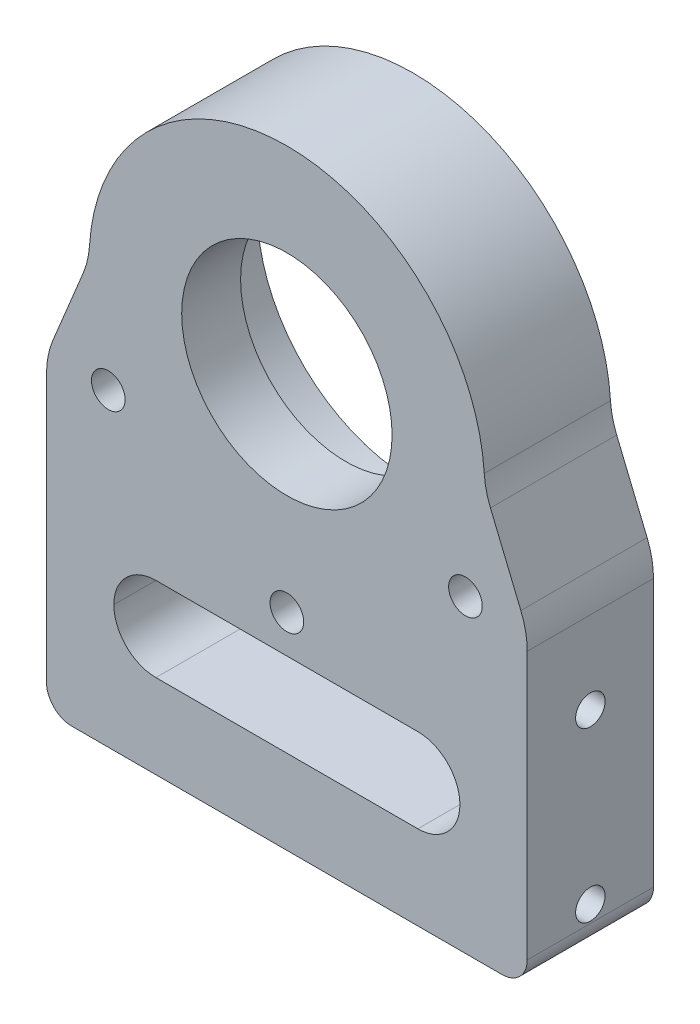
SolidWorks part; units mm, degrees
material "5052-H34"
ref_plane "正面" through (0, 0, 0) normal (0, 0, 1) x (1, 0, 0)
ref_plane "平面" through (0, 0, 0) normal (0, 1, 0) x (1, 0, 0)
ref_plane "右側面" through (0, 0, 0) normal (1, 0, 0) x (0, 0, -1)
sketch "ｽｹｯﾁ1" plane through (0, 0, 0) normal (0, 0, 1) x (1, 0, 0)
  line L1 (28.56, 15) -> (-28.56, 15)
  line L2 (28.56, 15) -> (28.56, -15)
  line L3 (28.56, -15) -> (-28.56, -15)
  line L4 (-28.56, 15) -> (-28.56, -15)
  line L5 (28.56, 15) -> (-28.56, -15) construction
  line L6 (28.56, -15) -> (-28.56, 15) construction
  point P0 (0, 0)
  dimension "D1" = 30
  dimension "D2" = 57.12
extrude "ﾎﾞｽ - 押し出し1" add sketch "ｽｹｯﾁ1" along normal blind 15
sketch "ｽｹｯﾁ2" plane through (-28.56, 0, 0) normal (-1, 0, 0) x (0, 0, 1)
  line L0 (7.5, 15) -> (7.5, -15) construction
  line L1 (15, 15) -> (0, 15) construction
  line L2 (15, -15) -> (0, -15) construction
  line L3 (7.5, -15) -> (7.5, 0) construction
  line L4 (7.5, 0) -> (0, 0) construction
  circle A0 centre (7.5, 10) radius 1.75
  circle A1 centre (7.5, -10) radius 1.75
  dimension "D1" = 3.5
  dimension "D2" = 5
extrude "ｶｯﾄ - 押し出し1" cut sketch "ｽｹｯﾁ2" against normal through all
sketch "ｽｹｯﾁ4" plane through (0, 0, 15) normal (0, 0, 1) x (1, 0, 0)
  line L0 (0, 0) -> (0, 34) construction
  line L1 (-28.56, 15) -> (-28.56, 34)
  line L2 (28.56, 15) -> (28.56, 34)
  circle A0 centre (0, 34) radius 18.5
  circle A1 centre (0, 34) radius 28.56
  line M8 (28.56, 15) -> (-28.56, 15)
  dimension "D1" = 37
  dimension "D2" = 34
extrude "ﾎﾞｽ - 押し出し4" add sketch "ｽｹｯﾁ4" against normal through all contours A1 L1 M8 | A1 A0 M8 | A1 L2 M8 region at (-26.4459, 19.6212, 15) region at (0, 61.8167, 15) region at (26.4459, 19.6212, 15)
sketch "ｽｹｯﾁ5" plane through (0, 0, 15) normal (0, 0, 1) x (1, 0, 0)
  circle A0 centre (0, 34) radius 18.5
  circle A1 centre (0, 34) radius 12.5
  dimension "D1" = 25
  dimension "D2" = 37
extrude "ﾎﾞｽ - 押し出し5" add sketch "ｽｹｯﾁ5" against normal blind 7
sketch "ｽｹｯﾁ6" plane through (0, 0, 8) normal (0, 0, -1) x (-1, 0, 0)
  circle A0 centre (0, 34) radius 17.5
  circle A1 centre (0, 34) radius 18.5
  dimension "D1" = 35
  dimension "D2" = 37
extrude "ﾎﾞｽ - 押し出し6" add sketch "ｽｹｯﾁ6" along normal blind 1
fillet "ﾌｨﾚｯﾄ1" radius 3 2 edges at (-28.56, -15, 7.5) (28.56, -15, 7.5)
sketch "ｽｹｯﾁ7" plane through (0, 0, 0) normal (0, 0, -1) x (-1, 0, 0)
  line L0 (0, 34) -> (0, 0) construction
  line L1 (0, 34) -> (-21.2176, 21.75) construction
  circle A0 centre (0, 9.5) radius 2
  circle A1 centre (-21.2176, 21.75) radius 2
  circle A2 centre (21.2176, 21.75) radius 2
  dimension "D1" = 24.5
  dimension "D2" = 4
  dimension "D5" = 4
  dimension "D3" = 24.5
  dimension "D4" = 60
extrude "ｶｯﾄ - 押し出し2" cut sketch "ｽｹｯﾁ7" against normal through all
sketch "ｽｹｯﾁ8" plane through (0, 0, 0) normal (0, 0, -1) x (-1, 0, 0)
  line L0 (-21.2176, 21.75) -> (-28.56, 21.75) construction
  line L1 (-28.56, -12) -> (-28.56, 34) construction
  line L2 (-28.56, 21.75) -> (-23.5, 34)
  line L3 (0, 34) -> (0, 0) construction
  line L4 (28.56, 21.75) -> (23.5, 34)
  line L5 (21.2176, 21.75) -> (28.56, 21.75) construction
  line L7 (28.56, 0) -> (-28.56, 0)
  line L8 (28.56, 0) -> (28.56, 34)
  line L9 (28.56, 34) -> (-28.56, 34)
  line L10 (-28.56, 0) -> (-28.56, 34)
  line L11 (28.56, 0) -> (-28.56, 34) construction
  line L12 (28.56, 34) -> (-28.56, 0) construction
  circle A0 centre (0, 34) radius 28.56
  circle A1 centre (0, 34) radius 23.5
  point P15 (0, 17)
  line M11 (28.56, -12) -> (28.56, 34)
  arc M12 (28.56, 34) -> (-28.56, 34) centre (0, 34) ccw
  line M13 (-28.56, 34) -> (-28.56, -12)
  dimension "D1" = 57.12
  dimension "D2" = 47
extrude "ｶｯﾄ - 押し出し3" cut sketch "ｽｹｯﾁ8" against normal through all contours L9 A0 L2 | A0 L2 M13 | A1 L9 M12 | L4 A0 L9 | A0 L4 M11 region at (28.1224, 26.1252, 0) region at (26.5423, 30.9215, 0) region at (0, 61.9214, 0) region at (-28.1224, 26.1252, 0) region at (-26.5423, 30.9215, 0)
fillet "ﾌｨﾚｯﾄ2" radius 10 4 edges at (-28.56, 21.75, 7.5) (28.56, 21.75, 7.5) (23.5, 34, 7.5) (-23.5, 34, 7.5)
sketch "ｽｹｯﾁ9" plane through (0, 0, 0) normal (0, 0, -1) x (-1, 0, 0)
  line L0 (25.56, -15) -> (-25.56, -15) construction
  line L1 (20.56, 5) -> (-20.56, 5)
  line L2 (20.56, 5) -> (20.56, -5)
  line L3 (20.56, -5) -> (-20.56, -5)
  line L4 (-20.56, 5) -> (-20.56, -5)
  line L5 (20.56, 5) -> (-20.56, -5) construction
  line L6 (20.56, -5) -> (-20.56, 5) construction
  line L7 (-28.56, -12) -> (-28.56, 19.766) construction
  line L8 (28.56, 19.766) -> (28.56, -12) construction
  point P0 (0, 0)
  dimension "D1" = 10
  dimension "D2" = 10
  dimension "D3" = 8
  dimension "D4" = 8
extrude "ｶｯﾄ - 押し出し4" cut sketch "ｽｹｯﾁ9" against normal through all
fillet "ﾌｨﾚｯﾄ3" radius 5 4 edges at (-20.56, 5, 7.5) (-20.56, -5, 7.5) (20.56, 5, 7.5) (20.56, -5, 7.5)
